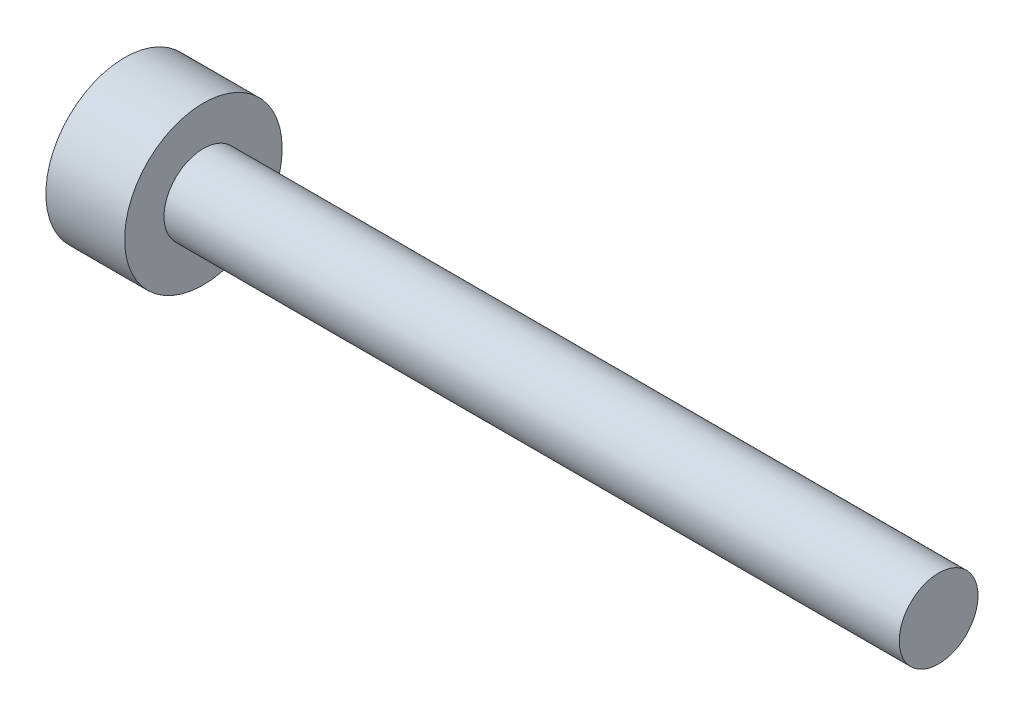
SolidWorks part; units mm, degrees
material "AISI 1045 Steel, cold drawn"
ref_plane "前视基准面" through (0, 0, 0) normal (0, 0, 1) x (1, 0, 0)
ref_plane "上视基准面" through (0, 0, 0) normal (0, 1, 0) x (1, 0, 0)
ref_plane "右视基准面" through (0, 0, 0) normal (1, 0, 0) x (0, 0, -1)
sketch "Sketch1" plane through (0, 0, 0) normal (1, 0, 0) x (0, 0, -1)
  circle A0 centre (0, 0) radius 3
  dimension "D1" = 6
extrude "Boss-Extrude1" add sketch "Sketch1" along normal blind 3
sketch "Sketch2" plane through (3, 0, 0) normal (1, 0, 0) x (0, 0, -1)
  circle A0 centre (0, 0) radius 1.5
  dimension "D1" = 3
extrude "Boss-Extrude2" add sketch "Sketch2" along normal blind 28
